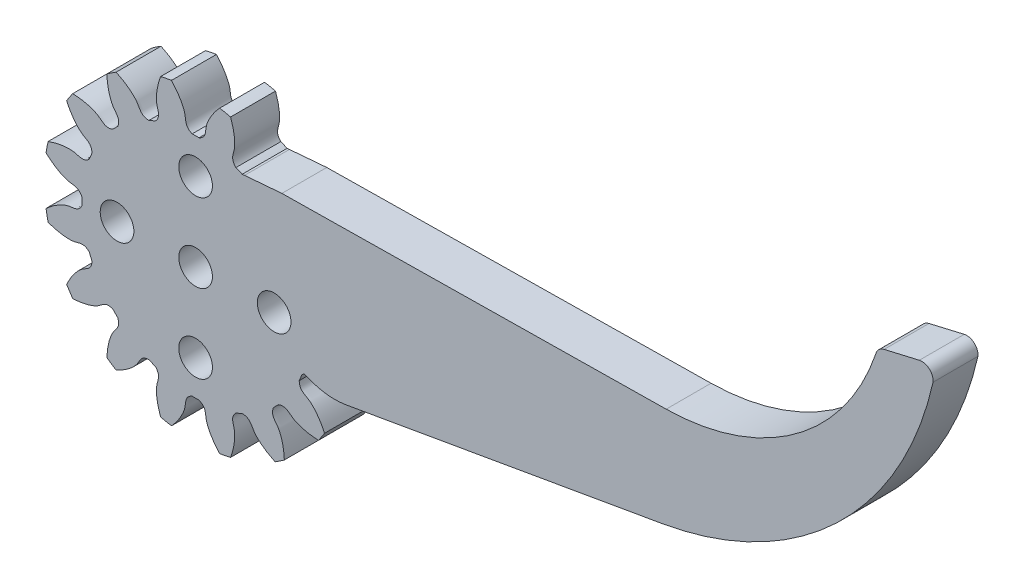
SolidWorks part; units mm, degrees
material "Thornel Mat VMA"
ref_plane "前视基准面" through (0, 0, 0) normal (0, 0, 1) x (1, 0, 0)
ref_plane "上视基准面" through (0, 0, 0) normal (0, 1, 0) x (1, 0, 0)
ref_plane "右视基准面" through (0, 0, 0) normal (1, 0, 0) x (0, 0, -1)
other "Configuration Table"
sketch "草图1" plane through (0, 0, 0) normal (0, 0, 1) x (1, 0, 0)
  circle A0 centre (0, 0) radius 13.5
extrude "凸台-拉伸1" add sketch "草图1" along normal blind 4
ref_axis "基准轴1" through (0, 0, -1.5) along (0, 0, 1)
sketch "草图2" plane through (0, 0, 0) normal (0, 0, 1) x (1, 0, 0)
  line L0 (0, 0) -> (0, 13.5) construction
  circle A0 centre (0, 0) radius 13.5 construction
  arc A1 (0.305, 10.1204) -> (-0.305, 10.1204) centre (0, 0) ccw
  arc A2 (4.6827, 15.2441) -> (-4.6827, 15.2441) centre (0, 0) ccw
  spline S0 degree 3 poles (0.305, 10.1204) (0.9628, 10.3952) (0.854, 10.906) (0.9672, 11.3802) (0.9768, 11.4173) (0.9884, 11.4586) (1.0021, 11.5039) (1.0181, 11.5533) (1.0366, 11.6065) (1.0577, 11.6636) (1.0816, 11.7245) (1.1084, 11.7891) (1.1383, 11.8573) (1.1715, 11.9289) (1.2081, 12.0039) (1.2482, 12.0822) (1.292, 12.1636) (1.3397, 12.2481) (1.3913, 12.3354) (1.447, 12.4256) (1.507, 12.5184) (1.5714, 12.6138) (1.6402, 12.7115) (1.7136, 12.8115) (1.7918, 12.9135) (1.8748, 13.0175) (1.9628, 13.1233) (2.0558, 13.2307) (2.1539, 13.3396) (2.2573, 13.4498) (2.366, 13.5612) (2.4802, 13.6735) (2.5998, 13.7866) (2.7251, 13.9003) (2.856, 14.0144) (2.9925, 14.1288) (3.1349, 14.2433) (3.2831, 14.3577) (3.4372, 14.4717) (3.5972, 14.5853) (3.7632, 14.6982) (3.9352, 14.8102) (4.1132, 14.9211) (4.3612, 15.0689) (4.5525, 15.1751) (4.6827, 15.2441) knots 0 0 0 0 0.200958 0.205848 0.21139 0.217584 0.224431 0.231929 0.240079 0.248881 0.258335 0.268441 0.2792 0.29061 0.302672 0.315386 0.328753 0.342771 0.357441 0.372764 0.388738 0.405364 0.422643 0.440573 0.459155 0.47839 0.498276 0.518814 0.540005 0.561847 0.584342 0.607488 0.631287 0.655737 0.68084 0.706594 0.733001 0.760059 0.78777 0.816132 0.845147 0.874814 0.905132 0.936103 1 1 1 1
  spline S1 degree 3 poles (-0.305, 10.1204) (-0.9628, 10.3952) (-0.854, 10.906) (-0.9672, 11.3802) (-0.9768, 11.4173) (-0.9884, 11.4586) (-1.0021, 11.5039) (-1.0181, 11.5533) (-1.0366, 11.6065) (-1.0577, 11.6636) (-1.0816, 11.7245) (-1.1084, 11.7891) (-1.1383, 11.8573) (-1.1715, 11.9289) (-1.2081, 12.0039) (-1.2482, 12.0822) (-1.292, 12.1636) (-1.3397, 12.2481) (-1.3913, 12.3354) (-1.447, 12.4256) (-1.507, 12.5184) (-1.5714, 12.6138) (-1.6402, 12.7115) (-1.7136, 12.8115) (-1.7918, 12.9135) (-1.8748, 13.0175) (-1.9628, 13.1233) (-2.0558, 13.2307) (-2.1539, 13.3396) (-2.2573, 13.4498) (-2.366, 13.5612) (-2.4802, 13.6735) (-2.5998, 13.7866) (-2.7251, 13.9003) (-2.856, 14.0144) (-2.9925, 14.1288) (-3.1349, 14.2433) (-3.2831, 14.3577) (-3.4372, 14.4717) (-3.5972, 14.5853) (-3.7632, 14.6982) (-3.9352, 14.8102) (-4.1132, 14.9211) (-4.3612, 15.0689) (-4.5525, 15.1751) (-4.6827, 15.2441) knots 0 0 0 0 0.200958 0.205848 0.21139 0.217584 0.224431 0.231929 0.240079 0.248881 0.258335 0.268441 0.2792 0.29061 0.302672 0.315386 0.328753 0.342771 0.357441 0.372764 0.388738 0.405364 0.422643 0.440573 0.459155 0.47839 0.498276 0.518814 0.540005 0.561847 0.584342 0.607488 0.631287 0.655737 0.68084 0.706594 0.733001 0.760059 0.78777 0.816132 0.845147 0.874814 0.905132 0.936103 1 1 1 1
extrude "切除-拉伸1" cut sketch "草图2" along normal through all
pattern_circular "阵列(圆周)1" count 16 every 22.5 about axis through (0, 0, -1.5) along (0, 0, 1) of "切除-拉伸1"
sketch "草图3" plane through (0, 0, 0) normal (0, 0, 1) x (1, 0, 0)
  circle A0 centre (0, 0) radius 12 construction
  dimension "Dn" = 24
sketch "草图4" plane through (0, 0, 4) normal (0, 0, 1) x (1, 0, 0)
  line L0 (0, 0) -> (0, 22.6625) construction
  line L8 (5.3353, 9.4908) -> (0, 0)
  line L14 (41.931, 9.9938) -> (5.3353, 9.4908)
  line L15 (64.488, 25.0473) -> (61.3481, 24.3151)
  line L16 (13.4179, -3.9332) -> (41.6, 0.9883)
  line L17 (0, 0) -> (10.3685, -3.6734)
  line L18 (0, 0) -> (3.336, 10.3639) construction
  arc A15 (10.3685, -3.6734) -> (13.4179, -3.9332) centre (12.3857, 1.9774) ccw
  arc A16 (41.931, 9.9938) -> (60.6267, 23.658) centre (41.6561, 29.9919) ccw
  arc A17 (61.3481, 24.3151) -> (60.6267, 23.658) centre (61.5752, 23.3413) ccw
  arc A18 (65.709, 23.9628) -> (64.488, 25.0473) centre (64.7151, 24.0734) ccw
  arc A19 (41.6, 0.9883) -> (65.709, 23.9628) centre (36.4391, 30.5411) ccw
  circle A20 centre (0, 0) radius 10.8876 construction
  spline S1 degree 3 poles (3.1194, 13.1347) (3.1665, 13.0052) (3.2376, 12.7917) (3.3197, 12.4967) (3.3755, 12.2596) (3.4185, 12.0381) (3.4498, 11.833) (3.4709, 11.6447) (3.4832, 11.4737) (3.4881, 11.3204) (3.4872, 11.2039) (3.4833, 11.1024) (3.4784, 11.0304) (3.4706, 10.9519) (3.4637, 10.8982) (3.3846, 10.4027) (3.0886, 9.9723) (3.5911, 9.4668) knots 0.46188 0.46188 0.46188 0.46188 0.52161 0.559427 0.594636 0.627236 0.657229 0.684614 0.70939 0.731559 0.751119 0.759921 0.775569 0.782416 0.794152 0.799042 1 1 1 1 construction
  point P21 (0, 0)
extrude "凸台-拉伸2" add sketch "草图4" against normal blind 4
sketch "草图6" plane through (0, 0, 4) normal (0, 0, 1) x (1, 0, 0)
  line L0 (0, 0) -> (0, 16.4393) construction
  line L1 (0, 0) -> (18.078, 0) construction
  circle A0 centre (0, 0) radius 7 construction
  circle A1 centre (0, 7) radius 1.5
  circle A2 centre (7, 0) radius 1.5
  circle A3 centre (0, -7) radius 1.5
  circle A4 centre (-7, 0) radius 1.5
  circle A5 centre (0, 0) radius 1.5
  dimension "D1" = 14
  dimension "D2" = 3
  dimension "D3" = 3
  dimension "D4" = 3
extrude "切除-拉伸3" cut sketch "草图6" against normal blind 5
sketch "草图7" plane through (0, 0, 4) normal (0, 0, 1) x (1, 0, 0)
  line L0 (4.1547, 9.2333) -> (7.6895, 9.5231)
  arc A0 (7.9084, 10.9411) -> (7.0818, 11.4934) centre (0, 0) ccw construction
  arc A1 (7.9084, 10.9411) -> (7.0818, 11.4934) centre (0, 0) ccw
  spline S0 degree 3 poles (-1577.3628, 1233.3375) (26.9406, -19.6509) (1.7604, 5.3297) (5.257, 10.1554) (5.3006, 10.2119) (5.3644, 10.2879) (5.4433, 10.3747) (5.5383, 10.4712) (5.6501, 10.5762) (5.7797, 10.6884) (5.9278, 10.8066) (6.095, 10.9295) (6.282, 11.0557) (6.4892, 11.1839) (6.6758, 11.2892) (6.8354, 11.3733) (29.1432, 22.5512) (107.9945, -82.093) (-1768.8285, 931.0004) knots -2.366572 -2.366572 -2.366572 -2.366572 0.200958 0.205848 0.217584 0.231929 0.248881 0.268441 0.29061 0.315386 0.342771 0.372764 0.405364 0.440573 0.47839 0.498276 0.518814 11.29839 11.29839 11.29839 11.29839 only from (4.1547, 9.2333) to (7.0818, 11.4934) construction
  spline S1 degree 3 poles (1537.0186, -1277.8939) (-117.1709, 68.3581) (9.682, 35.5547) (7.8885, 10.6232) (7.8661, 10.4026) (7.8305, 10.1524) (7.7883, 9.9217) (7.7478, 9.7419) (3.8521, -5.4045) (-70.7541, -1.5337) (-1628.2908, 1159.0037) knots -10.298357 -10.298357 -10.298357 -10.298357 0.481186 0.501724 0.540845 0.577357 0.611262 0.642559 0.657229 7.393143 7.393143 7.393143 7.393143 only from (7.9084, 10.9411) to (7.6895, 9.5231) construction
  spline S2 degree 3 poles (4.1547, 9.2333) (4.8675, 9.2355) (4.9625, 9.7491) (5.257, 10.1554) (5.3006, 10.2119) (5.3644, 10.2879) (5.4433, 10.3747) (5.5383, 10.4712) (5.6501, 10.5762) (5.7797, 10.6884) (5.9278, 10.8066) (6.095, 10.9295) (6.282, 11.0557) (6.4892, 11.1839) (6.717, 11.3125) (6.9172, 11.4152) (7.0415, 11.4745) (7.0818, 11.4934) knots 0 0 0 0 0.200958 0.205848 0.217584 0.231929 0.248881 0.268441 0.29061 0.315386 0.342771 0.372764 0.405364 0.440573 0.47839 0.518814 0.53812 0.53812 0.53812 0.53812
  spline S3 degree 3 poles (7.9084, 10.9411) (7.9024, 10.8035) (7.8863, 10.579) (7.8492, 10.2751) (7.8101, 10.0346) (7.7651, 9.8136) (7.7237, 9.6454) (7.6975, 9.5509) (7.6895, 9.5231) knots 0.46188 0.46188 0.46188 0.46188 0.52161 0.559427 0.594636 0.627236 0.657229 0.669752 0.669752 0.669752 0.669752
extrude "切除-拉伸4" cut sketch "草图7" against normal blind 10 contours S3 A1 S2 L0 region at (6.5574, 10.2336, 4)
sketch "草图10" plane through (0, 0, 4) normal (0, 0, 1) x (1, 0, 0)
  circle A0 centre (0, 0) radius 12 construction
  dimension "D1" = 24
